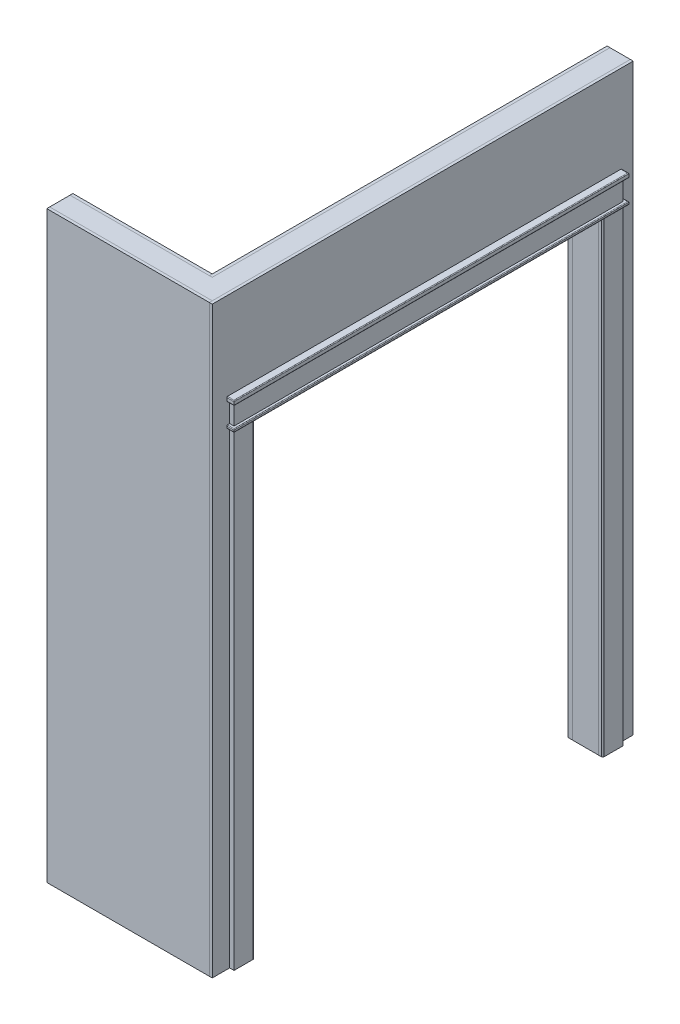
SolidWorks part; units mm, degrees
ref_plane "Front Plane" through (0, 0, 0) normal (0, 0, 1) x (1, 0, 0)
ref_plane "Top Plane" through (0, 0, 0) normal (0, 1, 0) x (1, 0, 0)
ref_plane "Right Plane" through (0, 0, 0) normal (1, 0, 0) x (0, 0, -1)
sketch "Sketch1" plane through (0, 0, 0) normal (0, 1, 0) x (1, 0, 0)
  line L1 (0, 0) -> (3581.4, 0)
  line L2 (0, 0) -> (0, 3479.8)
  line L3 (0, 3479.8) -> (3581.4, 3479.8)
  line L4 (3581.4, 0) -> (3581.4, 3479.8)
  line L9 (0, 76.2) -> (774.7, 76.2)
  line L10 (0, 1230.0171) -> (46.8505, 1230.0171)
  line L11 (0, 1230.0171) -> (0, 1143)
  line L12 (0, 1143) -> (46.8505, 1143)
  line L13 (46.8505, 1230.0171) -> (46.8505, 1143)
  line L14 (0, 76.2) -> (12.7, 76.2)
  line L15 (0, 977.9) -> (12.7, 977.9)
  line L16 (0, 977.9) -> (0, 850.9)
  line L17 (0, 850.9) -> (12.7, 850.9)
  line L18 (12.7, 977.9) -> (12.7, 850.9)
  line L19 (0, 76.2) -> (0, 0)
  line L20 (0, 0) -> (12.7, 0)
  line L21 (12.7, 76.2) -> (12.7, 0)
  arc A0 (0, 848.6682) -> (774.7, 76.2) centre (1.1159, 75.0841) cw
  dimension "D1" = 3581.4
  dimension "D2" = 3479.8
  dimension "D8" = 774.7
  dimension "D9" = 12.7
  dimension "D10" = 76.2
  dimension "D11" = 0
  dimension "D12" = 2249.7829
sketch "Sketch2" plane through (0, 0, 0) normal (0, 1, 0) x (1, 0, 0)
  line L0 (0, 0) -> (0, 3479.8) construction
  line L1 (0, 1739.9) -> (622.3, 1739.9)
  line L2 (0, 1739.9) -> (0, 1651)
  line L3 (0, 1651) -> (622.3, 1651)
  line L4 (622.3, 1739.9) -> (622.3, 1651)
  line L5 (0, 3479.8) -> (3581.4, 3479.8) construction
  dimension "D1" = 622.3
  dimension "D2" = 88.9
  dimension "D3" = 1739.9
extrude "Sole Plate 1" add sketch "Sketch2" along normal blind 38.1
sketch "Sketch3" plane through (0, 0, 0) normal (0, 1, 0) x (1, 0, 0)
  line L0 (711.2, 330.372) -> (711.2, 50330.372) construction
  line L1 (711.2, 1651) -> (622.3, 1651)
  line L2 (711.2, 1651) -> (711.2, 1784.35)
  line L3 (711.2, 1784.35) -> (622.3, 1784.35)
  line L4 (622.3, 1651) -> (622.3, 1784.35)
  line L5 (-1000, 3479.8) -> (49000, 3479.8) construction
  line L6 (0, 0) -> (0, 3479.8) construction
  line L7 (711.2, 3479.8) -> (622.3, 3479.8)
  line L8 (711.2, 3479.8) -> (711.2, 3346.45)
  line L9 (711.2, 3346.45) -> (622.3, 3346.45)
  line L10 (622.3, 3479.8) -> (622.3, 3346.45)
  line L12 (622.3, 1739.9) -> (0, 1739.9) construction
  dimension "D1" = 88.9
  dimension "D2" = 133.35
  dimension "D3" = 133.35
  dimension "D4" = 0
  dimension "D5" = 88.9
  dimension "D6" = 711.2
  dimension "D7" = 1562.1
  dimension "D8" = 1739.9
extrude "Sole Plate 2" add sketch "Sketch3" along normal blind 38.1 separate body
sketch "Sketch5" plane through (0, 38.1, 0) normal (0, 1, 0) x (1, 0, 0)
  line L1 (711.2, 1651) -> (622.3, 1651)
  line L2 (711.2, 1651) -> (711.2, 1689.1)
  line L3 (711.2, 1689.1) -> (622.3, 1689.1)
  line L4 (622.3, 1651) -> (622.3, 1689.1)
  line L9 (711.2, 1784.35) -> (622.3, 1784.35) construction
  line L10 (711.2, 1651) -> (711.2, 1784.35) construction
  line L14 (0, 1651) -> (622.3, 1651) construction
  line L15 (622.3, 1739.9) -> (0, 1739.9) construction
  line L16 (0, 1739.9) -> (38.1, 1739.9)
  line L17 (0, 1739.9) -> (0, 1651)
  line L18 (0, 1651) -> (38.1, 1651)
  line L19 (38.1, 1739.9) -> (38.1, 1651)
  line L20 (406.4, 1739.9) -> (444.5, 1739.9)
  line L21 (406.4, 1739.9) -> (406.4, 1651)
  line L22 (406.4, 1651) -> (444.5, 1651)
  line L23 (444.5, 1739.9) -> (444.5, 1651)
  line L24 (622.3, 1784.35) -> (622.3, 1651) construction
  line L25 (711.2, 3346.45) -> (711.2, 3479.8) construction
  line L26 (622.3, 3479.8) -> (711.2, 3479.8)
  line L27 (622.3, 3479.8) -> (622.3, 3441.7)
  line L28 (622.3, 3441.7) -> (711.2, 3441.7)
  line L29 (711.2, 3479.8) -> (711.2, 3441.7)
  line L30 (711.2, 1746.25) -> (622.3, 1746.25)
  line L31 (711.2, 1746.25) -> (711.2, 1708.15)
  line L32 (711.2, 1708.15) -> (622.3, 1708.15)
  line L33 (622.3, 1746.25) -> (622.3, 1708.15)
  line L34 (622.3, 3479.8) -> (622.3, 3346.45) construction
  line L35 (622.3, 3422.65) -> (711.2, 3422.65)
  line L36 (622.3, 3422.65) -> (622.3, 3384.55)
  line L37 (622.3, 3384.55) -> (711.2, 3384.55)
  line L38 (711.2, 3422.65) -> (711.2, 3384.55)
  line L39 (622.3, 3346.45) -> (711.2, 3346.45) construction
  dimension "D1" = 88.9
  dimension "D2" = 38.1
  dimension "D3" = 0
  dimension "D6" = 38.1
  dimension "D7" = 38.1
  dimension "D8" = 406.4
  dimension "D9" = 38.1
  dimension "D10" = 38.1
  dimension "D11" = 38.1
  dimension "D12" = 38.1
  dimension "D13" = 76.2
extrude "Framing Studs" add sketch "Sketch5" along normal blind 2438.4 separate body
sketch "Sketch6" plane through (0, 38.1, 0) normal (0, 1, 0) x (1, 0, 0)
  line L1 (622.3, 3346.45) -> (711.2, 3346.45)
  line L2 (622.3, 3346.45) -> (622.3, 3384.55)
  line L3 (622.3, 3384.55) -> (711.2, 3384.55)
  line L4 (711.2, 3346.45) -> (711.2, 3384.55)
  line L5 (622.3, 1784.35) -> (711.2, 1784.35)
  line L6 (622.3, 1784.35) -> (622.3, 1746.25)
  line L7 (622.3, 1746.25) -> (711.2, 1746.25)
  line L8 (711.2, 1784.35) -> (711.2, 1746.25)
  dimension "D1" = 38.1
extrude "Jack Studs" add sketch "Sketch6" along normal blind 2030.4125 separate body
sketch "Sketch7" plane through (0, 2068.5125, 0) normal (0, 1, 0) x (1, 0, 0)
  line L0 (622.3, 1746.25) -> (711.2, 1746.25) construction
  line L1 (622.3, 1746.25) -> (711.2, 1746.25)
  line L2 (622.3, 1746.25) -> (622.3, 3384.55)
  line L3 (622.3, 3384.55) -> (711.2, 3384.55)
  line L4 (711.2, 1746.25) -> (711.2, 3384.55)
  line L5 (622.3, 1784.35) -> (622.3, 1746.25) construction
  dimension "D1" = 0
extrude "Header" add sketch "Sketch7" along normal blind 38.1 separate body
sketch "Sketch8" plane through (0, 2106.6125, 0) normal (0, 1, 0) x (1, 0, 0)
  line L1 (622.3, 1746.25) -> (711.2, 1746.25)
  line L2 (622.3, 1746.25) -> (622.3, 1784.35)
  line L3 (622.3, 1784.35) -> (711.2, 1784.35)
  line L4 (711.2, 1746.25) -> (711.2, 1784.35)
  line L5 (622.3, 2152.65) -> (711.2, 2152.65)
  line L6 (622.3, 3384.55) -> (711.2, 3384.55)
  line L7 (622.3, 3384.55) -> (622.3, 3346.45)
  line L8 (622.3, 3346.45) -> (711.2, 3346.45)
  line L9 (711.2, 3384.55) -> (711.2, 3346.45)
  line L10 (622.3, 2152.65) -> (622.3, 2190.75)
  line L11 (622.3, 2190.75) -> (711.2, 2190.75)
  line L12 (711.2, 2152.65) -> (711.2, 2190.75)
  line L13 (622.3, 2559.05) -> (711.2, 2559.05)
  line L14 (622.3, 2559.05) -> (622.3, 2597.15)
  line L15 (622.3, 2597.15) -> (711.2, 2597.15)
  line L16 (711.2, 2559.05) -> (711.2, 2597.15)
  line L17 (622.3, 2965.45) -> (711.2, 2965.45)
  line L18 (622.3, 2965.45) -> (622.3, 3003.55)
  line L19 (622.3, 3003.55) -> (711.2, 3003.55)
  line L20 (711.2, 2965.45) -> (711.2, 3003.55)
  dimension "D1" = 38.1
  dimension "D2" = 38.1
  dimension "D3" = 4
extrude "Cripple Studs" add sketch "Sketch8" along normal up to surface (369.8875 mm away) separate body up to face at (666.75, 2476.5, -3403.6)
sketch "Sketch9" plane through (0, 2476.5, 0) normal (0, 1, 0) x (1, 0, 0)
  line L0 (622.3, 3479.8) -> (622.3, 3441.7) construction
  line L1 (622.3, 1739.9) -> (0, 1739.9)
  line L2 (622.3, 1739.9) -> (622.3, 1651)
  line L3 (622.3, 1651) -> (0, 1651)
  line L4 (0, 1739.9) -> (0, 1651)
  line L5 (711.2, 1651) -> (622.3, 1651)
  line L6 (711.2, 1651) -> (711.2, 3479.8)
  line L7 (711.2, 3479.8) -> (622.3, 3479.8)
  line L8 (622.3, 1651) -> (622.3, 3479.8)
  line L9 (711.2, 3479.8) -> (622.3, 3479.8) construction
  line M14 (711.2, 1651) -> (711.2, 1689.1)
  line M15 (711.2, 1689.1) -> (622.3, 1689.1)
  line M16 (622.3, 1689.1) -> (622.3, 1651)
  line M17 (622.3, 1651) -> (711.2, 1651)
extrude "Top Plate 1" add sketch "Sketch9" along normal blind 38.1 separate body contours L3 L2 L1 | L8 L2 L5 L6 L7 | M17 M14 M15 M16 region at (311.15, 2476.5, -1695.45) region at (666.75, 2476.5, -2584.45) region at (666.75, 2476.5, -1670.05)
sketch "Sketch10" plane through (0, 0, -1739.9) normal (0, 0, -1) x (-1, 0, 0)
  line L1 (0, 2552.7) -> (-622.3, 2552.7)
  line L2 (0, 2552.7) -> (0, 0)
  line L3 (0, 0) -> (-622.3, 0)
  line L4 (-622.3, 2552.7) -> (-622.3, 0)
extrude "Inside Side Wall Dry Wall" add sketch "Sketch10" along normal blind 12.7 separate body
sketch "Sketch11" plane through (622.3, 0, 0) normal (-1, 0, 0) x (0, 0, 1)
  line L0 (-1739.9, 0) -> (-1739.9, 2552.7)
  line L1 (-1739.9, 2552.7) -> (-3479.8, 2552.7)
  line L2 (-3479.8, 2552.7) -> (-3479.8, 0)
  line L3 (-3479.8, 0) -> (-3346.45, 0)
  line L4 (-3346.45, 0) -> (-3346.45, 2068.5125)
  line L5 (-3346.45, 2068.5125) -> (-1784.35, 2068.5125)
  line L6 (-1784.35, 2068.5125) -> (-1784.35, 0)
  line L7 (-1784.35, 0) -> (-1739.9, 0)
  line L8 (-1739.9, 2514.6) -> (-3479.8, 2514.6) construction
  dimension "D1" = 38.1
extrude "Inside Main Wall Dry Wall" add sketch "Sketch11" along normal blind 12.7 separate body
sketch "Sketch12" plane through (0, 0, -1651) normal (0, 0, 1) x (1, 0, 0)
  line L0 (711.2, 38.1) -> (711.2, 0) construction
  line L1 (0, 2552.7) -> (711.2, 2552.7)
  line L2 (0, 2552.7) -> (0, 0)
  line L3 (0, 0) -> (711.2, 0)
  line L4 (711.2, 2552.7) -> (711.2, 0)
  line L5 (622.3, 0) -> (711.2, 0) construction
extrude "Outside Side Wall Dry Wall" add sketch "Sketch12" along normal blind 12.7 separate body
sketch "Sketch13" plane through (711.2, 0, 0) normal (1, 0, 0) x (0, 0, -1)
  line L0 (3479.8, 0) -> (3346.45, 0)
  line L1 (3346.45, 0) -> (3346.45, 2068.5125)
  line L2 (3346.45, 2068.5125) -> (1784.35, 2068.5125)
  line L3 (1784.35, 2068.5125) -> (1784.35, 0)
  line L4 (1784.35, 0) -> (1638.3, 0)
  line L5 (1638.3, 0) -> (1638.3, 2552.7)
  line L6 (1638.3, 2552.7) -> (3479.8, 2552.7)
  line L7 (3479.8, 2552.7) -> (3479.8, 0)
  line L9 (1651, 2476.5) -> (3479.8, 2476.5) construction
  dimension "D1" = 76.2
extrude "Outside Main Wall Dry Wall" add sketch "Sketch13" along normal blind 12.7 separate body
sketch "Sketch21" plane through (0, 2514.6, 0) normal (0, 1, 0) x (1, 0, 0)
  line L0 (622.3, 3479.8) -> (622.3, 1739.9)
  line L1 (622.3, 1739.9) -> (0, 1739.9)
  line L2 (0, 1739.9) -> (0, 1651)
  line L3 (0, 1651) -> (711.2, 1651)
  line L4 (711.2, 1651) -> (711.2, 3479.8)
  line L5 (711.2, 3479.8) -> (622.3, 3479.8)
  line L6 (711.2, 1651) -> (0, 1651) construction
extrude "Top Plate 2" add sketch "Sketch21" along normal blind 38.1 separate body
sketch "Sketch14" plane through (723.9, 0, 0) normal (1, 0, 0) x (0, 0, -1)
  line L0 (1784.35, 2068.5125) -> (3346.45, 2068.5125) construction
  line L1 (1803.4, 0) -> (1714.5, 0)
  line L2 (1803.4, 0) -> (1803.4, 2049.4625)
  line L3 (1803.4, 2049.4625) -> (1714.5, 2049.4625)
  line L4 (1714.5, 0) -> (1714.5, 2049.4625)
  line L5 (1701.8, 2062.1625) -> (3429, 2062.1625)
  line L6 (3327.4, 0) -> (3416.3, 0)
  line L7 (3327.4, 0) -> (3327.4, 2049.4625)
  line L8 (3327.4, 2049.4625) -> (3416.3, 2049.4625)
  line L9 (3416.3, 0) -> (3416.3, 2049.4625)
  line L10 (1714.5, 2049.4625) -> (3429, 2049.4625)
  line L11 (1701.8, 2062.1625) -> (1701.8, 2049.4625)
  line L12 (3429, 2049.4625) -> (1701.8, 2049.4625)
  line L13 (3429, 2049.4625) -> (3429, 2062.1625)
  line L14 (1714.5, 2062.1625) -> (3416.3, 2062.1625)
  line L15 (1714.5, 2062.1625) -> (1714.5, 2151.0625)
  line L16 (1714.5, 2151.0625) -> (3416.3, 2151.0625)
  line L17 (3416.3, 2062.1625) -> (3416.3, 2151.0625)
  line L18 (1701.8, 2170.1125) -> (3429, 2170.1125)
  line L19 (1701.8, 2170.1125) -> (1701.8, 2151.0625)
  line L20 (1701.8, 2151.0625) -> (3429, 2151.0625)
  line L21 (3429, 2170.1125) -> (3429, 2151.0625)
  line L22 (1701.8, 2049.4625) -> (1714.5, 2049.4625)
  line M4 (1638.3, 0) -> (1784.35, 0)
  line M5 (1784.35, 0) -> (1784.35, 2068.5125)
  line M6 (1784.35, 2068.5125) -> (3346.45, 2068.5125)
  line M7 (3346.45, 2068.5125) -> (3346.45, 0)
  line M8 (3346.45, 0) -> (3479.8, 0)
  dimension "D2" = 88.9
  dimension "D3" = 88.9
  dimension "D4" = 0
  dimension "D5" = 12.7
  dimension "D8" = 88.9
  dimension "D9" = 19.05
  dimension "D10" = 19.05
  dimension "D11" = 0
  dimension "D12" = 0
  dimension "D13" = 12.7
  dimension "D16" = 0
  dimension "D17" = 0
  dimension "D18" = 12.7
extrude "Casing Flat" add sketch "Sketch14" along normal blind 19.05 separate body contours L4 L3 M4 M5 | L17 L16 L15 | L9 L8 M8 M7 | M5 M7 M6 | L2 L3 L1 M5 | L8 L7 L6 M7 region at (723.9, 1024.7312, -1793.875) region at (723.9, 1024.7312, -1749.425) region at (723.9, 1024.7312, -3336.925) region at (723.9, 2065.3375, -2565.4) region at (723.9, 2109.5086, -2565.4) region at (723.9, 1024.7312, -3381.375)
extrude "Casing Fillet" add sketch "Sketch14<3>" along normal blind 31.75 contours L21 L18 L19 L20 L16 | L3 L10 L8 L5 M7 M5 | L12 L3 L5 L11 M5 | L10 L13 L5 L8 M7 region at (723.9, 2055.8125, -2565.4) region at (723.9, 2055.8125, -1743.075) region at (723.9, 2055.8125, -3387.725) region at (723.9, 2160.5875, -2565.4)
sketch "Sketch14<3>" plane through (723.9, 0, 0) normal (1, 0, 0) x (0, 0, -1) same geometry as "Sketch14"
fillet "Fillet1" radius 3.175 12 edges at (739.775, 2170.1125, -1701.8) (739.775, 2151.0625, -1701.8) (755.65, 2170.1125, -2565.4) (755.65, 2151.0625, -2565.4) (739.775, 2170.1125, -3429) (739.775, 2151.0625, -3429) (739.775, 2049.4625, -3429) (739.775, 2049.4625, -1701.8) (755.65, 2049.4625, -2565.4) (739.775, 2062.1625, -3429) (755.65, 2062.1625, -2565.4) (739.775, 2062.1625, -1701.8)
fillet "Fillet2" radius 6.35 2 edges at (742.95, 1024.7312, -1803.4) (742.95, 1024.7312, -3327.4)
sketch "Sketch17" plane through (0, 2068.5125, 0) normal (0, -1, 0) x (-1, 0, 0)
  line L0 (-622.3, 3346.45) -> (-711.2, 3346.45) construction
  line L1 (-609.6, 1784.35) -> (-723.9, 1784.35)
  line L2 (-609.6, 1784.35) -> (-609.6, 3346.45)
  line L3 (-609.6, 3346.45) -> (-723.9, 3346.45)
  line L4 (-723.9, 1784.35) -> (-723.9, 3346.45)
  dimension "D1" = 114.3
  dimension "D2" = 0
extrude "Trim Door Top" add sketch "Sketch17" along normal blind 19.05 separate body
sketch "Sketch18" plane through (0, 0, -3346.45) normal (0, 0, -1) x (-1, 0, 0)
  line L1 (-723.9, 2049.4625) -> (-609.6, 2049.4625)
  line L2 (-723.9, 2049.4625) -> (-723.9, 0)
  line L3 (-723.9, 0) -> (-609.6, 0)
  line L4 (-609.6, 2049.4625) -> (-609.6, 0)
extrude "Trim Door Right" add sketch "Sketch18" against normal blind 19.05 separate body
sketch "Sketch19" plane through (0, 0, -1784.35) normal (0, 0, -1) x (-1, 0, 0)
  line L1 (-723.9, 2049.4625) -> (-609.6, 2049.4625)
  line L2 (-723.9, 2049.4625) -> (-723.9, 0)
  line L3 (-723.9, 0) -> (-609.6, 0)
  line L4 (-609.6, 2049.4625) -> (-609.6, 0)
extrude "Trim Door Left" add sketch "Sketch19" along normal blind 19.05 separate body
sketch "Sketch20" plane through (609.6, 0, 0) normal (-1, 0, 0) x (0, 0, 1)
  line L0 (-1784.35, 0) -> (-1739.9, 0) construction
  line L1 (-1803.4, 0) -> (-1752.4958, 0)
  line L2 (-1803.4, 0) -> (-1803.4, 2049.7823)
  line L3 (-1803.4, 2049.7823) -> (-1752.4958, 2049.7823)
  line L4 (-1752.4958, 0) -> (-1752.4958, 2049.7823)
  line L5 (-3327.4, 0) -> (-3416.3, 0)
  line L6 (-3327.4, 0) -> (-3327.4, 2049.7823)
  line L7 (-3327.4, 2049.7823) -> (-3416.3, 2049.7823)
  line L8 (-3416.3, 0) -> (-3416.3, 2049.7823)
  line L9 (-3416.3, 2049.7823) -> (-1752.4958, 2049.7823)
  line L10 (-3416.3, 2049.7823) -> (-3416.3, 2138.6823)
  line L11 (-3416.3, 2138.6823) -> (-1752.4958, 2138.6823)
  line L12 (-1752.4958, 2049.7823) -> (-1752.4958, 2138.6823)
  line M6 (-3346.45, 0) -> (-3346.45, 2068.5125)
  line M7 (-3346.45, 2068.5125) -> (-1784.35, 2068.5125)
  line M8 (-1784.35, 2068.5125) -> (-1784.35, 0)
  dimension "D2" = 88.9
  dimension "D3" = 88.9
extrude "Casing Door interior Sides" add sketch "Sketch20" along normal blind 19.05 separate body contours L3 L2 L1 L4 | L7 L6 L5 L8
extrude "Casing Door Interior Top" add sketch "Sketch20<4>" along normal blind 19.05 separate body contours L3 L12 L11 L10 L7 M6 M7 M8 | L7 L9 L3 M8 M7 M6 region at (609.6, 2059.1474, -2565.4) region at (609.6, 2102.8838, -2589.0826)
sketch "Sketch20<4>" plane through (609.6, 0, 0) normal (-1, 0, 0) x (0, 0, 1) same geometry as "Sketch20"
sketch "Sketch23" plane through (0, 38.1, 0) normal (0, 1, 0) x (1, 0, 0)
  line L0 (622.3, 1739.9) -> (0, 1739.9) construction
  line L1 (622.3, 1651) -> (584.2, 1651)
  line L2 (622.3, 1651) -> (622.3, 1739.9)
  line L3 (622.3, 1739.9) -> (584.2, 1739.9)
  line L4 (584.2, 1651) -> (584.2, 1739.9)
  dimension "D1" = 38.1
extrude "Boss-Extrude1" add sketch "Sketch23" along normal blind 2438.4 separate body
